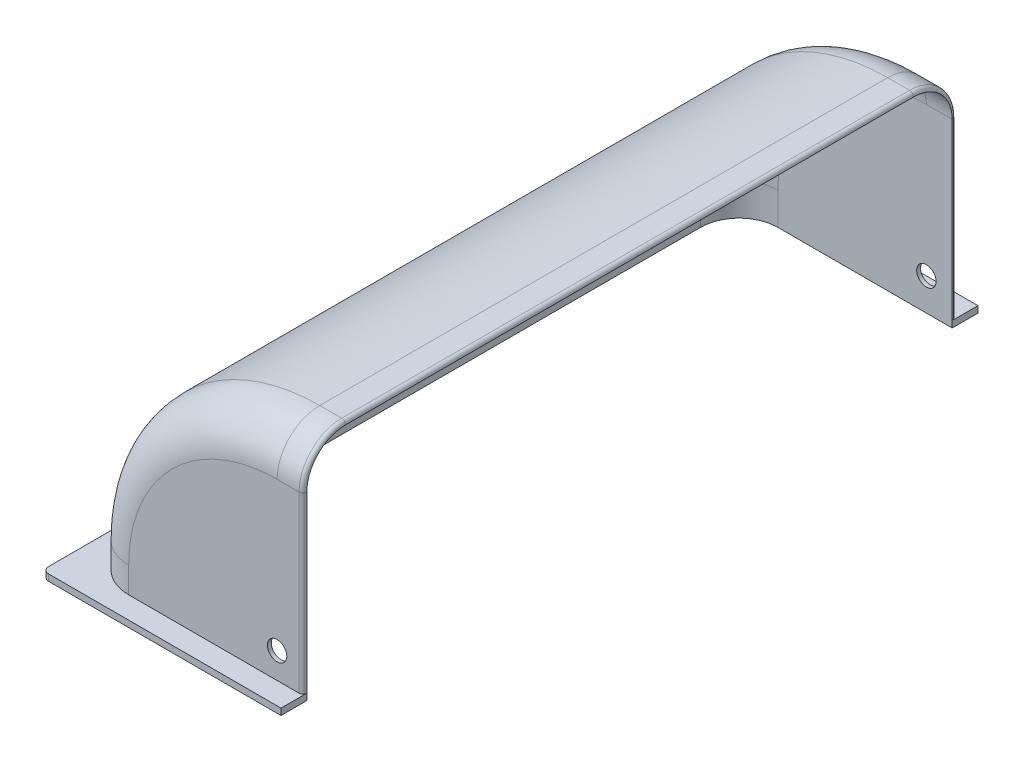
SolidWorks part; units mm, degrees
ref_plane "Front Plane" through (0, 0, 0) normal (0, 0, 1) x (1, 0, 0)
ref_plane "Top Plane" through (0, 0, 0) normal (0, 1, 0) x (1, 0, 0)
ref_plane "Right Plane" through (0, 0, 0) normal (1, 0, 0) x (0, 0, -1)
sketch "Sketch1" plane through (0, 0, 0) normal (0, 1, 0) x (1, 0, 0)
  line L0 (0, -250) -> (0, 250) construction
  line L2 (-165, 270) -> (-165, -270)
  line L5 (-165, 270) -> (0, 0) construction
  line L6 (-165, -270) -> (0, 0) construction
  line L9 (-145, -250) -> (-145, 250)
  line L11 (-145, 250) -> (0, 250)
  line L12 (-165, 270) -> (0, 270)
  line L21 (-145, -250) -> (0, -250)
  line L22 (-165, -270) -> (0, -270)
  line L23 (0, 250) -> (0, 270)
  line L24 (0, -250) -> (0, -270)
  point P0 (0, 0)
  point P9 (0, 0)
  dimension "D1" = 20
  dimension "D2" = 540
  dimension "D3" = 20
  dimension "D4" = 20
  dimension "D5" = 165
  dimension "D6" = 165
extrude "Boss-Extrude1" add sketch "Sketch1" along normal blind 5
sketch "Sketch7" plane through (0, 5, 0) normal (0, 1, 0) x (1, 0, 0)
  line L0 (0, 253) -> (-148, 253)
  line L1 (0, 250) -> (-145, 250)
  line L2 (0, 250) -> (0, -250) construction
  line L3 (0, -250) -> (-145, -250)
  line L4 (-145, 250) -> (-145, -250)
  line L5 (-148, 253) -> (-148, -253)
  line L6 (0, -253) -> (-148, -253)
  line L7 (0, 253) -> (0, 250)
  line L8 (0, -250) -> (0, -253)
  dimension "D1" = 3
extrude "Boss-Extrude3" add sketch "Sketch7" along normal blind 20
fillet "Fillet5" radius 30 2 edges at (-145, 12.5, -250) (-145, 12.5, 250)
fillet "Fillet6" radius 33 2 edges at (-148, 15, 253) (-148, 15, -253)
fillet "Fillet4" radius 5 2 edges at (-165, 2.5, -270) (-165, 2.5, 270)
sketch "Sketch8" plane through (0, 25, 0) normal (0, 1, 0) x (1, 0, 0)
  line L0 (0, 253) -> (-115, 253)
  line L1 (0, 250) -> (-115, 250)
  line L2 (0, -250) -> (-115, -250)
  line L3 (-145, 220) -> (-145, -220)
  line L4 (-148, 220) -> (-148, -220)
  line L5 (0, -253) -> (-115, -253)
  line L6 (0, -253) -> (0, -250)
  line L7 (0, 250) -> (0, 253)
  arc A0 (-115, -250) -> (-145, -220) centre (-115, -220) cw
  arc A1 (-115, 250) -> (-145, 220) centre (-115, 220) ccw
  arc A2 (-115, 253) -> (-148, 220) centre (-115, 220) ccw
  arc A3 (-115, -253) -> (-148, -220) centre (-115, -220) cw
  point P3 (0, 0)
  dimension "D1" = 30
revolve "Revolve3" add sketch "Sketch8" angle 90 about L7
sketch "Sketch3" plane through (0, 0, 0) normal (0, -1, 0) x (1, 0, 0)
  line L5 (0, 250) -> (-115, 250) construction
  line L6 (0, 253) -> (-115, 253)
  line L7 (0, 250) -> (-115, 250)
  line L9 (0, -250) -> (-115, -250)
  line L10 (-145, 220) -> (-145, -220)
  line L11 (-148, 220) -> (-148, -220)
  line L12 (0, -253) -> (-115, -253)
  line L15 (0, -253) -> (0, -250)
  line L16 (0, 250) -> (0, 253)
  arc A0 (-115, -250) -> (-145, -220) centre (-115, -220) cw
  arc A1 (-115, 250) -> (-145, 220) centre (-115, 220) ccw
  arc A2 (-115, 253) -> (-148, 220) centre (-115, 220) ccw
  arc A3 (-115, -253) -> (-148, -220) centre (-115, -220) cw
  point P5 (0, 0)
  dimension "D3" = 30
  dimension "D4" = 30
  dimension "D1" = 500
  dimension "D2" = 145
  dimension "D5" = 3
sketch "Sketch9" plane through (0, 0, 0) normal (1, 0, 0) x (0, 0, -1)
  line L0 (253, 25) -> (253, 140)
  line L1 (250, 25) -> (250, 140)
  line L2 (-250, 25) -> (-250, 140)
  line L3 (220, 170) -> (-220, 170)
  line L4 (220, 173) -> (-220, 173)
  line L5 (-253, 25) -> (-253, 140)
  line L6 (-253, 25) -> (-250, 25) construction
  line L7 (250, 25) -> (253, 25) construction
  line L8 (0, 0) -> (0, 25) construction
  line L9 (-220, 0) -> (220, 0) construction
  line L10 (-220, 25) -> (220, 25) construction
  line L11 (-250, 25) -> (-250, 0)
  line L12 (-250, 0) -> (-270, 0)
  line L13 (-270, 0) -> (-270, 5)
  line L14 (-270, 5) -> (-253, 5)
  line L15 (-253, 5) -> (-253, 25)
  line L16 (250, 25) -> (250, 0)
  line L17 (250, 0) -> (270, 0)
  line L18 (270, 0) -> (270, 5)
  line L19 (270, 5) -> (253, 5)
  line L20 (253, 5) -> (253, 25)
  arc A0 (-250, 140) -> (-220, 170) centre (-220, 140) cw
  arc A1 (250, 140) -> (220, 170) centre (220, 140) ccw
  arc A2 (253, 140) -> (220, 173) centre (220, 140) ccw
  arc A3 (-253, 140) -> (-220, 173) centre (-220, 140) cw
  point P3 (0, 25)
  dimension "D1" = 30
extrude "Boss-Extrude4" add sketch "Sketch9" along normal blind 20
sketch "Sketch10" plane through (0, 0, 253) normal (0, 0, 1) x (1, 0, 0)
  line L0 (-250, 25) -> (20, 25) construction
  line L1 (20, 140) -> (20, 5) construction
  line L2 (20, 25) -> (0, 25) construction
  line L3 (0, 25) -> (0, 140) construction
  circle A1 centre (0, 25) radius 7.5
  point P4 (-115, 25)
  dimension "D2" = 15
  dimension "D1" = 20
extrude "Cut-Extrude1" cut sketch "Sketch10" against normal up to surface (506 mm away) up to face at (-42.7635, 67.7635, -253)
fillet "Fillet7" radius 3 5 edges at (20, 72.5, -253) (20, 163.3345, -243.3345) (20, 72.5, 253) (20, 163.3345, 243.3345) (20, 173, 0)
